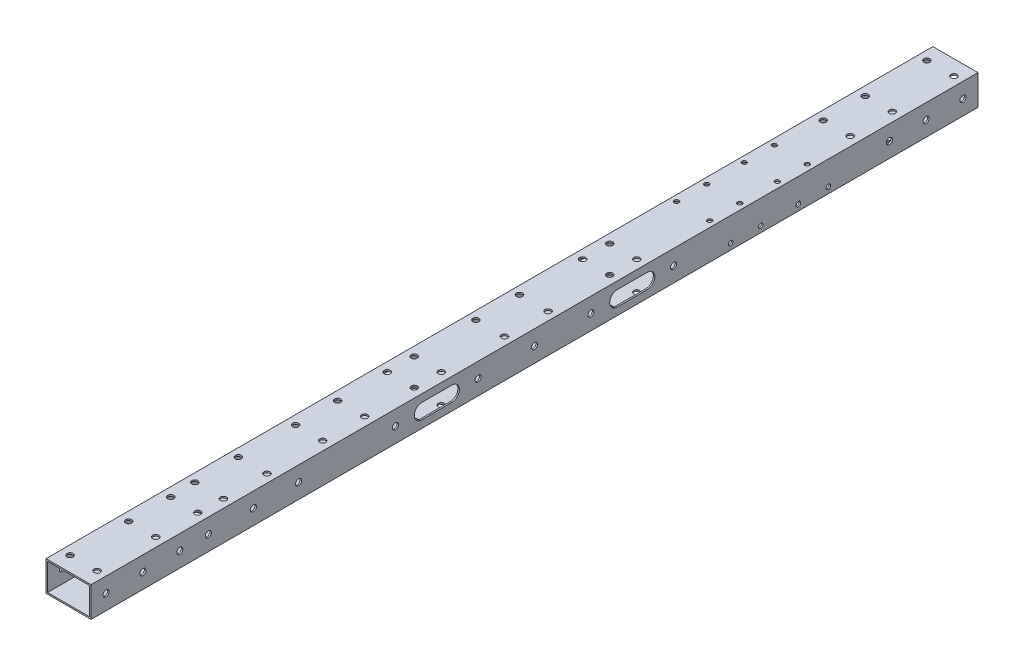
SolidWorks part; units mm, degrees
material "6063-T5"
ref_plane "前视基准面" through (0, 0, 0) normal (0, 0, 1) x (1, 0, 0)
ref_plane "上视基准面" through (0, 0, 0) normal (0, 1, 0) x (1, 0, 0)
ref_plane "右视基准面" through (0, 0, 0) normal (1, 0, 0) x (0, 0, -1)
sketch "草图1" plane through (0, 0, 0) normal (0, 0, 1) x (1, 0, 0)
  line L0 (-14, -9) -> (-14, 9)
  line L1 (-15, -10) -> (15, -10)
  line L2 (-15, -10) -> (-15, 10)
  line L3 (-15, 10) -> (15, 10)
  line L4 (15, -10) -> (15, 10)
  line L5 (0, 10) -> (0, -10) construction
  line L6 (-15, 0) -> (15, 0) construction
  line L7 (-14, 9) -> (14, 9)
  line L8 (14, -9) -> (14, 9)
  line L9 (-14, -9) -> (14, -9)
  point P0 (0, 0)
  dimension "D1" = 20
  dimension "D2" = 30
  dimension "D3" = 1
extrude "凸台-拉伸1" add sketch "草图1" along normal mid plane 590
sketch "草图2" [suppressed] plane through (15, 0, 0) normal (1, 0, 0) x (0, 0, -1)
  line L0 (-295, 10) -> (295, 10) construction
  line L1 (209, 10) -> (295, 10)
  line L2 (209, 10) -> (209, -10)
  line L3 (209, -10) -> (295, -10)
  line L4 (295, 10) -> (295, -10)
  dimension "D1" = 86
extrude "切除-拉伸1" [suppressed] cut sketch "草图2" against normal blind 60
sketch "草图4" [suppressed] plane through (0, 10, 0) normal (0, 1, 0) x (1, 0, 0)
  circle A0 centre (0, 0) radius 5
  dimension "D1" = 10
extrude "切除-拉伸3" [suppressed] cut sketch "草图4" against normal mid plane 64
sketch "草图5" plane through (0, 9, 0) normal (0, -1, 0) x (1, 0, 0)
  line L0 (-15, 295) -> (-15, -295) construction
  line L1 (-9.5, 14.5) -> (9.5, 14.5) construction
  line L2 (-9.5, 14.5) -> (-9.5, -14.5) construction
  line L3 (-9.5, -14.5) -> (9.5, -14.5) construction
  line L4 (9.5, 14.5) -> (9.5, -14.5) construction
  line L5 (-9.5, 14.5) -> (9.5, -14.5) construction
  line L6 (-9.5, -14.5) -> (9.5, 14.5) construction
  line L7 (-9.5, 201.5) -> (9.5, 201.5) construction
  line L8 (-9.5, 201.5) -> (-9.5, 172.5) construction
  line L13 (-9.5, 172.5) -> (9.5, 172.5) construction
  line L14 (9.5, 201.5) -> (9.5, 172.5) construction
  line L15 (-15, 295) -> (15, 295) construction
  line L16 (15, 295) -> (15, -295) construction
  line L17 (-9.5, -172.5) -> (9.5, -172.5) construction
  line L18 (-9.5, -172.5) -> (-9.5, -201.5) construction
  line L19 (-9.5, -201.5) -> (9.5, -201.5) construction
  line L20 (9.5, -172.5) -> (9.5, -201.5) construction
  line L21 (-15, -295) -> (15, -295) construction
  circle A4 centre (9.5, -201.5) radius 1.65 construction
  circle A5 centre (9.5, -172.5) radius 1.65 construction
  circle A6 centre (-9.5, -201.5) radius 1.65 construction
  circle A7 centre (-9.5, -172.5) radius 1.65 construction
  circle A8 centre (-9.5, -172.5) radius 2.025
  circle A9 centre (9.5, -172.5) radius 2.025
  circle A10 centre (-9.5, -201.5) radius 2.025
  circle A11 centre (9.5, -201.5) radius 2.025
  circle A20 centre (9.5, 172.5) radius 1.65 construction
  circle A21 centre (-9.5, 172.5) radius 1.65 construction
  circle A22 centre (9.5, 201.5) radius 1.65 construction
  circle A23 centre (-9.5, 201.5) radius 1.65 construction
  circle A24 centre (9.5, -14.5) radius 1.65 construction
  circle A25 centre (9.5, 14.5) radius 1.65 construction
  circle A26 centre (-9.5, -14.5) radius 1.65 construction
  circle A27 centre (-9.5, 14.5) radius 1.65 construction
  circle A28 centre (-9.5, -14.5) radius 2.025
  circle A29 centre (9.5, -14.5) radius 2.025
  circle A30 centre (-9.5, 14.5) radius 2.025
  circle A31 centre (9.5, 14.5) radius 2.025
  circle A32 centre (-9.5, 172.5) radius 2.025
  circle A33 centre (-9.5, 201.5) radius 2.025
  circle A34 centre (9.5, 201.5) radius 2.025
  circle A35 centre (9.5, 172.5) radius 2.025
  point P1 (0, 0)
  point P3 (-9.5, 187)
  dimension "D1" = 4.05
  dimension "D2" = 29
  dimension "D5" = 29
  dimension "D3" = 19
  dimension "D4" = 19
  dimension "D6" = 5.5
  dimension "D7" = 93.5
  dimension "D8" = 5.5
  dimension "D9" = 5.5
  dimension "D10" = 122.5
  dimension "D11" = 29
extrude "切除-拉伸4" cut sketch "草图5" against normal mid plane 10
sketch "草图7" plane through (0, -9, 0) normal (0, 1, 0) x (1, 0, 0)
  circle A0 centre (-9.5, 201.5) radius 3.8
  circle A1 centre (9.5, 201.5) radius 3.8
  circle A2 centre (-9.5, 172.5) radius 3.8
  circle A3 centre (9.5, 172.5) radius 3.8
  circle A4 centre (-9.5, 14.5) radius 3.8
  circle A5 centre (9.5, 14.5) radius 3.8
  circle A6 centre (-9.5, -14.5) radius 3.8
  circle A7 centre (9.5, -14.5) radius 3.8
  circle A8 centre (-9.5, -172.5) radius 3.8
  circle A9 centre (9.5, -172.5) radius 3.8
  circle A10 centre (-9.5, -201.5) radius 3.8
  circle A11 centre (9.5, -201.5) radius 3.8
  dimension "D1" = 7.6
extrude "切除-拉伸5" cut sketch "草图7" against normal mid plane 10
sketch "草图8" [suppressed] plane through (15, 0, 0) normal (1, 0, 0) x (0, 0, -1)
  circle A0 centre (-151, 0) radius 2.025 construction
  circle A1 centre (-185, 0) radius 2.025 construction
  circle A2 centre (-219, 0) radius 2.025 construction
  circle A3 centre (-151, 0) radius 2.025
  circle A4 centre (-185, 0) radius 2.025
  circle A5 centre (-219, 0) radius 2.025
  circle A6 centre (36, 0) radius 2.025 construction
  circle A7 centre (2, 0) radius 2.025 construction
  circle A8 centre (-32, 0) radius 2.025 construction
  circle A9 centre (36, 0) radius 2.025
  circle A10 centre (2, 0) radius 2.025
  circle A11 centre (-32, 0) radius 2.025
extrude "切除-拉伸6" [suppressed] cut sketch "草图8" against normal blind 74
sketch "草图9" [suppressed] plane through (-15, 0, 0) normal (-1, 0, 0) x (0, 0, 1)
  circle A0 centre (-155, 0) radius 2.025 construction
  circle A1 centre (-189, 5) radius 1.525 construction
  circle A2 centre (-203, 0) radius 2.025 construction
  circle A3 centre (-155, 0) radius 2.025
  circle A4 centre (-189, 5) radius 1.525
  circle A5 centre (-203, 0) radius 2.025
extrude "切除-拉伸7" [suppressed] cut sketch "草图9" against normal blind 114
sketch "草图10" [suppressed] plane through (0, -10, 0) normal (0, -1, 0) x (1, 0, 0)
  circle A0 centre (0, -75) radius 2.025 construction
  circle A1 centre (0, -109) radius 2.025 construction
  circle A2 centre (0, -143) radius 2.025 construction
  circle A3 centre (0, -75) radius 2.025
  circle A4 centre (0, -109) radius 2.025
  circle A5 centre (0, -143) radius 2.025
extrude "切除-拉伸8" [suppressed] cut sketch "草图10" against normal blind 70
sketch "草图11" plane through (15, 0, 0) normal (1, 0, 0) x (0, 0, -1)
  line L0 (-295, -10) -> (-295, 10) construction
  line L1 (-295, 10) -> (295, 10) construction
  circle A9 centre (-236, 0) radius 2.025 construction
  circle A10 centre (-260.5, 0) radius 2.025 construction
  circle A11 centre (-285, 0) radius 2.025 construction
  circle A12 centre (217, 0) radius 2.025
  circle A13 centre (187, 0) radius 2.025
  circle A14 centre (157, 0) radius 2.025
  circle A15 centre (30, 0) radius 2.025
  circle A16 centre (0, 0) radius 2.025
  circle A17 centre (-30, 0) radius 2.025
  circle A18 centre (-157, 0) radius 2.025
  circle A19 centre (-187, 0) radius 2.025
  circle A20 centre (-217, 0) radius 2.025
  circle A21 centre (-236, 0) radius 2.025
  circle A22 centre (-260.5, 0) radius 2.025
  circle A23 centre (-285, 0) radius 2.025
  dimension "D1" = 30
  dimension "D3" = 78
  dimension "D4" = 30
  dimension "D5" = 30
  dimension "D6" = 10
  dimension "D7" = 127
  dimension "D8" = 127
  dimension "D9" = 30
  dimension "D10" = 30
  dimension "D2" = 30
extrude "切除-拉伸9" cut sketch "草图11" against normal blind 113
sketch "草图12" [suppressed] plane through (0, 10, 0) normal (0, 1, 0) x (1, 0, 0)
  circle A0 centre (0, 36.5) radius 2.025 construction
  circle A1 centre (0, 18.5) radius 2.025 construction
  circle A2 centre (0, 36.5) radius 2.025
  circle A3 centre (0, 18.5) radius 2.025
extrude "切除-拉伸10" [suppressed] cut sketch "草图12" against normal blind 80
sketch "草图13" [suppressed] plane through (-15, 0, 0) normal (-1, 0, 0) x (0, 0, 1)
  circle A0 centre (28, 0) radius 2.025 construction
  circle A1 centre (3.5, 0) radius 2.025 construction
  circle A2 centre (28, 0) radius 2.025
  circle A3 centre (3.5, 0) radius 2.025
extrude "切除-拉伸11" [suppressed] cut sketch "草图13" against normal blind 80
sketch "草图14" [suppressed] plane through (0, -9, 0) normal (0, 1, 0) x (1, 0, 0)
  circle A0 centre (-7.5, 45.55) radius 1.5 construction
  circle A1 centre (-7.5, 35.55) radius 1.5 construction
  circle A2 centre (7.5, 45.55) radius 1.5 construction
  circle A3 centre (7.5, 35.55) radius 1.5 construction
  circle A4 centre (7.5, 90.55) radius 1.5 construction
  circle A5 centre (7.5, 80.55) radius 1.5 construction
  circle A6 centre (-7.5, 90.55) radius 1.5 construction
  circle A7 centre (-7.5, 80.55) radius 1.5 construction
  circle A8 centre (-7.5, 45.55) radius 1.5
  circle A9 centre (-7.5, 35.55) radius 1.5
  circle A10 centre (7.5, 45.55) radius 1.5
  circle A11 centre (7.5, 35.55) radius 1.5
  circle A12 centre (7.5, 90.55) radius 1.5
  circle A13 centre (7.5, 80.55) radius 1.5
  circle A14 centre (-7.5, 90.55) radius 1.5
  circle A15 centre (-7.5, 80.55) radius 1.5
extrude "切除-拉伸12" [suppressed] cut sketch "草图14" against normal blind 10
sketch "草图15" [suppressed] plane through (0, -10, 0) normal (0, -1, 0) x (1, 0, 0)
  circle A0 centre (9, 66) radius 2.025 construction
  circle A1 centre (-9, 66) radius 2.025 construction
  circle A2 centre (9, 94) radius 2.025 construction
  circle A3 centre (-9, 94) radius 2.025 construction
  circle A4 centre (9, 66) radius 2.025
  circle A5 centre (-9, 66) radius 2.025
  circle A6 centre (9, 94) radius 2.025
  circle A7 centre (-9, 94) radius 2.025
extrude "切除-拉伸13" [suppressed] cut sketch "草图15" against normal up to surface (20 mm away)
sketch "草图16" [suppressed] plane through (-15, 0, 0) normal (-1, 0, 0) x (0, 0, 1)
  line L0 (0, 0) -> (0, 10) construction
  line L1 (84.5, 10) -> (-84.5, 10) construction
  circle A0 centre (59.5, 0) radius 1.525 construction
  circle A1 centre (79.5, 0) radius 1.525 construction
  circle A2 centre (59.5, 0) radius 1.525
  circle A3 centre (79.5, 0) radius 1.525
  circle A4 centre (-79.5, 0) radius 1.525
  circle A5 centre (-59.5, 0) radius 1.525
sketch "草图17" [suppressed] plane through (15, 0, 0) normal (1, 0, 0) x (0, 0, -1)
  circle A0 centre (94, 0) radius 1.525 construction
  circle A1 centre (66, 0) radius 1.525 construction
  circle A2 centre (94, 0) radius 1.525
  circle A3 centre (66, 0) radius 1.525
extrude "切除-拉伸14" [suppressed] cut sketch "草图16" against normal up to surface (30 mm away)
extrude "切除-拉伸15" [suppressed] cut sketch "草图17" against normal up to surface (30 mm away)
sketch "草图18" plane through (0, -10, 0) normal (0, -1, 0) x (1, 0, 0)
  line L0 (-429.5, 50) -> (160.5, 50) construction
  line L1 (-429.5, 80) -> (160.5, 80) construction
  line L2 (-15, 50) -> (15, 50) construction
  line L3 (-15, 80) -> (15, 80) construction
  line L4 (15, 295) -> (15, -295) construction
  line L5 (-15, 295) -> (-15, -295) construction
  line L6 (-15, 80) -> (15, 50) construction
  line L8 (-9, 56) -> (9, 56) construction
  line L9 (-9, 56) -> (-9, 74) construction
  line L10 (-9, 74) -> (9, 74) construction
  line L11 (9, 56) -> (9, 74) construction
  line L12 (0, 74) -> (0, 56) construction
  line L13 (-9, 65) -> (9, 65) construction
  circle A0 centre (-9, 74) radius 2.025
  circle A1 centre (9, 74) radius 2.025
  circle A2 centre (-9, 56) radius 2.025
  circle A3 centre (9, 56) radius 2.025
  point P4 (0, 65)
  dimension "D3" = 4.05
  dimension "D1" = 6
  dimension "D2" = 6
extrude "切除-拉伸16" cut sketch "草图18" against normal blind 90
mirror "镜向1" about plane through (0, 0, 0) normal (0, 0, 1) of "切除-拉伸16"
sketch "草图19" [suppressed] plane through (0, 10, 0) normal (0, 1, 0) x (1, 0, 0)
  line L0 (-15, -275) -> (15, -275) construction
  line L1 (-15, -295) -> (-15, 209) construction
  line L2 (15, -295) -> (-15, -295) construction
  line L3 (15, -295) -> (15, 209) construction
  line L4 (-15, -275) -> (15, -295) construction
  line L6 (-10, -290) -> (10, -290) construction
  line L7 (-10, -290) -> (-10, -280) construction
  line L8 (-10, -280) -> (10, -280) construction
  line L9 (10, -290) -> (10, -280) construction
  line L10 (0, -280) -> (0, -290) construction
  line L11 (-10, -285) -> (10, -285) construction
  circle A0 centre (-10, -285) radius 2.025
  circle A1 centre (10, -285) radius 2.025
  point P6 (0, -285)
  dimension "D4" = 4.05
  dimension "D1" = 20
  dimension "D2" = 5
  dimension "D3" = 5
extrude "切除-拉伸17" [suppressed] cut sketch "草图19" against normal blind 10
sketch "草图20" [suppressed] plane through (0, 10, 0) normal (0, 1, 0) x (1, 0, 0)
  circle A0 centre (-10, -151) radius 2.025 construction
  circle A1 centre (10, -151) radius 2.025 construction
  circle A2 centre (-10, -151) radius 2.025
  circle A3 centre (10, -151) radius 2.025
extrude "切除-拉伸18" [suppressed] cut sketch "草图20" against normal blind 10
sketch "草图21" plane through (15, 0, 0) normal (1, 0, 0) x (0, 0, -1)
  line L0 (-40, 290) -> (-40, -10) construction
  line L1 (-90, 290) -> (-90, -10) construction
  line L2 (-40, 10) -> (-40, -10) construction
  line L3 (-90, 10) -> (-90, -10) construction
  line L4 (-295, 10) -> (295, 10) construction
  line L5 (-90, 10) -> (-40, -10) construction
  line L6 (-84, 0) -> (-46, 0) construction
  circle A0 centre (-46, 0) radius 2.025
  circle A1 centre (-84, 0) radius 2.025
  point P11 (-65, 0)
  dimension "D2" = 4.05
  dimension "D1" = 6
extrude "切除-拉伸19" cut sketch "草图21" against normal blind 126
sketch "草图22" plane through (0, 10, 0) normal (0, 1, 0) x (1, 0, 0)
  line L0 (15, -275) -> (-15, -275) construction
  line L1 (15, -295) -> (15, 295) construction
  line L2 (-15, -295) -> (-15, 295) construction
  line L3 (15, -295) -> (-15, -295) construction
  line L4 (-15, -275) -> (15, -295) construction
  line L5 (-9, -285) -> (9, -285) construction
  line L6 (0, 0) -> (95.2431, 0) construction
  line L7 (-9, 285) -> (9, 285) construction
  line L8 (-15, 275) -> (15, 295) construction
  line L9 (15, 275) -> (-15, 275) construction
  circle A0 centre (9, -285) radius 2.025 construction
  circle A1 centre (-9, -285) radius 2.025 construction
  circle A2 centre (-9, 285) radius 2.025
  circle A3 centre (9, 285) radius 2.025
  point P13 (0, -285)
  point P25 (0, 285)
  dimension "D3" = 4.05
  dimension "D1" = 20
  dimension "D2" = 6
extrude "切除-拉伸20" cut sketch "草图22" against normal blind 10
sketch "草图23" [suppressed] plane through (-15, 0, 0) normal (-1, 0, 0) x (0, 0, 1)
  circle A0 centre (44, 0) radius 2.025 construction
  circle A1 centre (82, 0) radius 2.025 construction
  circle A2 centre (44, 0) radius 2.025
  circle A3 centre (82, 0) radius 2.025
extrude "切除-拉伸21" [suppressed] cut sketch "草图23" against normal blind 70
sketch "草图24" [suppressed] plane through (-15, 0, 0) normal (-1, 0, 0) x (0, 0, 1)
  circle A0 centre (44, 0) radius 4
  circle A1 centre (82, 0) radius 4
  dimension "D1" = 8
extrude "切除-拉伸22" [suppressed] cut sketch "草图24" against normal blind 10
sketch "草图25" [suppressed] plane through (0, -10, 0) normal (0, -1, 0) x (1, 0, 0)
  line L0 (-15, 46.025) -> (-15, 41.975) construction
  line L1 (-15, 84.025) -> (-15, 79.975) construction
  line L2 (-15, 46.025) -> (-15, 41.975) construction
  line L3 (-15, 84.025) -> (-15, 79.975) construction
  line L4 (-15, 82) -> (15, 82) construction
  line L5 (15, 295) -> (15, -209) construction
  line L6 (-15, 44) -> (15, 82) construction
  line L7 (0, 45.5) -> (0, 80.5) construction
  line L8 (-7, 45.5) -> (-7, 80.5)
  line L9 (7, 45.5) -> (7, 80.5)
  arc A0 (-7, 45.5) -> (7, 45.5) centre (0, 45.5) ccw
  arc A1 (7, 80.5) -> (-7, 80.5) centre (0, 80.5) ccw
  point P11 (0, 63)
  dimension "D1" = 7
  dimension "D2" = 35
extrude "切除-拉伸23" [suppressed] cut sketch "草图25" against normal blind 10 from surface
sketch "草图26" plane through (0, -10, 0) normal (0, -1, 0) x (1, 0, 0)
  line L0 (-11, 144) -> (-11, 124) construction
  line L1 (-15, 295) -> (-15, -295) construction
  line L2 (0, 0) -> (0, 192.5481) construction
  line L3 (11, 144) -> (11, 124) construction
  circle A0 centre (-11, 124) radius 1.525
  circle A1 centre (-11, 144) radius 1.525
  circle A2 centre (-9, 74) radius 2.025 construction
  circle A3 centre (11, 144) radius 1.525
  circle A4 centre (11, 124) radius 1.525
  dimension "D3" = 3.05
  dimension "D4" = 50
  dimension "D1" = 20
  dimension "D2" = 4
extrude "切除-拉伸24" cut sketch "草图26" against normal blind 10
sketch "草图27" plane through (-15, 0, 0) normal (-1, 0, 0) x (0, 0, 1)
  circle A0 centre (114, -6) radius 1.25 construction
  circle A1 centre (134, -6) radius 1.25 construction
  circle A2 centre (114, -6) radius 1.25 construction
  circle A3 centre (134, -6) radius 1.25 construction
  circle A4 centre (134, -6) radius 1.525
  circle A5 centre (114, -6) radius 1.525
  dimension "D1" = 3.05
extrude "切除-拉伸25" cut sketch "草图27" against normal blind 100
sketch "草图28" plane through (15, 0, 0) normal (1, 0, 0) x (0, 0, -1)
  line L0 (-53.975, 10) -> (-58.025, 10) construction
  line L1 (-71.975, 10) -> (-76.025, 10) construction
  line L2 (-53.975, 10) -> (-58.025, 10) construction
  line L3 (-71.975, 10) -> (-76.025, 10) construction
  line L4 (-74, 10) -> (-74, -10) construction
  line L5 (-295, -10) -> (295, -10) construction
  line L6 (-56, 10) -> (-56, -10) construction
  line L7 (-74, 0) -> (-56, 0) construction
  line L8 (-71, 0) -> (-59, 0) construction
  line L9 (-71, 5) -> (-59, 5)
  line L10 (-71, -5) -> (-59, -5)
  arc A0 (-71, 5) -> (-71, -5) centre (-71, 0) ccw
  arc A1 (-59, -5) -> (-59, 5) centre (-59, 0) ccw
  point P14 (-65, 0)
  dimension "D1" = 5
  dimension "D2" = 12
extrude "切除-拉伸26" cut sketch "草图28" against normal blind 100
mirror "镜向2" about plane through (0, 0, 0) normal (0, 0, 1) of "切除-拉伸26"
sketch "草图29" [suppressed] plane through (0, 10, 0) normal (0, 1, 0) x (1, 0, 0)
  circle A0 centre (-5.25, 9.0933) radius 1.7 construction
  circle A1 centre (5.25, 9.0933) radius 1.7 construction
  circle A2 centre (5.25, -9.0933) radius 1.7 construction
  circle A3 centre (-5.25, -9.0933) radius 1.7 construction
  circle A4 centre (-5.25, 9.0933) radius 1.7 construction
  circle A5 centre (5.25, 9.0933) radius 1.7 construction
  circle A6 centre (5.25, -9.0933) radius 1.7 construction
  circle A7 centre (-5.25, -9.0933) radius 1.7 construction
  circle A8 centre (5.25, 9.0933) radius 1.525
  circle A9 centre (-5.25, 9.0933) radius 1.525
  circle A10 centre (-5.25, -9.0933) radius 1.525
  circle A11 centre (5.25, -9.0933) radius 1.525
  dimension "D1" = 3.05
extrude "切除-拉伸27" [suppressed] cut sketch "草图29" against normal blind 60
sketch "草图30" [suppressed] plane through (15, 0, 0) normal (1, 0, 0) x (0, 0, -1)
  line L0 (10.6183, 10) -> (7.5683, 10) construction
  line L1 (-7.5683, 10) -> (-10.6183, 10) construction
  line L2 (10.6183, 10) -> (7.5683, 10) construction
  line L3 (-7.5683, 10) -> (-10.6183, 10) construction
  line L4 (-9.0933, 10) -> (-9.0933, -10) construction
  line L5 (-84.5, -10) -> (84.5, -10) construction
  line L6 (9.0933, 10) -> (9.0933, -10) construction
  line L7 (-6.5, 0) -> (6.5, 0) construction
  line L8 (-6.5, 5) -> (6.5, 5)
  line L9 (-6.5, -5) -> (6.5, -5)
  arc A0 (-6.5, 5) -> (-6.5, -5) centre (-6.5, 0) ccw
  arc A1 (6.5, -5) -> (6.5, 5) centre (6.5, 0) ccw
  point P12 (0, 0)
  dimension "D1" = 5
  dimension "D2" = 13
extrude "切除-拉伸28" [suppressed] cut sketch "草图30" against normal blind 60
sketch "草图31" plane through (0, 10, 0) normal (0, 1, 0) x (1, 0, 0)
  circle A4 centre (0, 72) radius 2.025 construction
  circle A5 centre (0, 132) radius 2.025 construction
  circle A6 centre (0, 72) radius 2.025
  circle A7 centre (0, 132) radius 2.025
extrude "切除-拉伸29" cut sketch "草图31" against normal blind 50
sketch "草图32" plane through (-15, 0, 0) normal (-1, 0, 0) x (0, 0, 1)
  circle A0 centre (46, 0) radius 3.75
  circle A1 centre (84, 0) radius 3.75
  dimension "D1" = 7.5
extrude "切除-拉伸30" cut sketch "草图32" against normal blind 10
sketch "草图33" [suppressed] plane through (0, 10, 0) normal (0, 1, 0) x (1, 0, 0)
  line L0 (0, -171) -> (0, -201) construction
  line L1 (6, -171) -> (6, -201)
  line L2 (-6, -171) -> (-6, -201)
  arc A0 (6, -171) -> (-6, -171) centre (0, -171) ccw
  arc A1 (-6, -201) -> (6, -201) centre (0, -201) ccw
  circle A2 centre (10, -151) radius 2.025 construction
  point P3 (0, -186)
  dimension "D2" = 6
  dimension "D1" = 20
  dimension "D3" = 30
extrude "切除-拉伸31" [suppressed] cut sketch "草图33" against normal up to surface (20 mm away)
sketch "草图34" [suppressed] plane through (0, 10, 0) normal (0, 1, 0) x (1, 0, 0)
  line L0 (15, -0.025) -> (15, 4.025) construction
  line L1 (15, -0.025) -> (15, 4.025) construction
  line L2 (15, 2) -> (-15, 2) construction
  line L3 (-15, -295) -> (-15, 209) construction
  line L4 (0, 2) -> (0, 17) construction
  circle A0 centre (0, 17) radius 1.525
  circle A1 centre (0, -13) radius 1.525
  dimension "D2" = 3.05
  dimension "D1" = 15
extrude "切除-拉伸32" [suppressed] cut sketch "草图34" against normal blind 50
sketch "草图36" plane through (0, 10, 0) normal (0, 1, 0) x (1, 0, 0)
  line L0 (15, -295) -> (15, 295) construction
  line L1 (-9, 244) -> (9, 244) construction
  line L2 (-9, 244) -> (-9, 216) construction
  line L3 (-9, 216) -> (9, 216) construction
  line L4 (9, 244) -> (9, 216) construction
  line L5 (-15, -295) -> (-15, 295) construction
  line L6 (15, 295) -> (-15, 295) construction
  circle A4 centre (-9, 244) radius 2.025
  circle A5 centre (-9, 216) radius 2.025
  circle A6 centre (9, 216) radius 2.025
  circle A7 centre (9, 244) radius 2.025
  dimension "D5" = 4.05
  dimension "D1" = 6
  dimension "D2" = 6
  dimension "D3" = 28
  dimension "D4" = 79
extrude "切除-拉伸33" cut sketch "草图36" against normal blind 37
sketch "草图37" plane through (0, -10, 0) normal (0, -1, 0) x (1, 0, 0)
  circle A0 centre (-9, -216) radius 3.8
  circle A1 centre (9, -216) radius 3.8
  circle A2 centre (-9, -244) radius 3.8
  circle A3 centre (9, -244) radius 3.8
  circle A4 centre (-9.5, -201.5) radius 3.8 construction
extrude "切除-拉伸34" cut sketch "草图37" against normal blind 10
mirror "镜向3" about plane through (0, 0, 0) normal (0, 0, 1) of "切除-拉伸34", "切除-拉伸33"
sketch "草图38" plane through (15, 0, 0) normal (1, 0, 0) x (0, 0, -1)
  circle A0 centre (-84, 0) radius 2.5
  circle A1 centre (-46, 0) radius 2.5
  dimension "D1" = 5
extrude "凸台-拉伸2" add sketch "草图38" against normal up to surface (1 mm away) up to face at (14, 0, 65)
sketch "草图39" plane through (-15, 0, 0) normal (-1, 0, 0) x (0, 0, 1)
  circle A0 centre (84, 0) radius 6
  circle A1 centre (46, 0) radius 6
  dimension "D1" = 12
extrude "凸台-拉伸3" add sketch "草图39" against normal up to surface (1 mm away) up to face at (-14, 0, 42.25)
sketch "草图40" plane through (0, 10, 0) normal (0, 1, 0) x (1, 0, 0)
  circle A0 centre (0, 72) radius 2.025
extrude "凸台-拉伸4" add sketch "草图40" against normal up to surface (1 mm away) up to face at (9, 9, 241.975)
sketch "草图41" plane through (0, -10, 0) normal (0, -1, 0) x (1, 0, 0)
  circle A0 centre (0, -72) radius 2.025
extrude "凸台-拉伸5" add sketch "草图41" against normal up to surface (1 mm away) up to face at (9, -9, 219.8)
sketch "草图42" plane through (-15, 0, 0) normal (-1, 0, 0) x (0, 0, 1)
  line L0 (-75, 0) -> (-55, 0) construction
  line L1 (-75, 5) -> (-55, 5)
  line L2 (-75, -5) -> (-55, -5)
  line L3 (-59, 5) -> (-71, 5) construction
  line L4 (0, 0) -> (0, 10) construction
  line L5 (295, 10) -> (-295, 10) construction
  line L6 (75, 0) -> (55, 0) construction
  line L7 (75, 5) -> (55, 5)
  line L8 (75, -5) -> (55, -5)
  arc A0 (-75, 5) -> (-75, -5) centre (-75, 0) ccw
  arc A1 (-55, -5) -> (-55, 5) centre (-55, 0) ccw
  arc A2 (75, 5) -> (75, -5) centre (75, 0) cw
  arc A3 (55, -5) -> (55, 5) centre (55, 0) cw
  point P2 (-65, 0)
  point P10 (-65, 5)
  point P13 (65, 0)
  dimension "D1" = 5
  dimension "D2" = 20
extrude "切除-拉伸36" cut sketch "草图42" against normal up to surface (30 mm away) up to face at (15, 0, 0)
sketch "草图43" plane through (-15, 0, 0) normal (-1, 0, 0) x (0, 0, 1)
  circle A0 centre (-30, 0) radius 2.5
  circle A1 centre (0, 0) radius 2.5
  circle A2 centre (30, 0) radius 2.5
  dimension "D1" = 5
extrude "凸台-拉伸6" add sketch "草图43" against normal up to surface (1 mm away) up to face at (-14, 0, -65)
sketch "草图44" plane through (15, 0, 0) normal (1, 0, 0) x (0, 0, -1)
  circle A0 centre (-30, 0) radius 2.5
  circle A1 centre (0, 0) radius 2.5
  circle A2 centre (30, 0) radius 2.5
  dimension "D1" = 5
extrude "凸台-拉伸7" add sketch "草图44" against normal up to surface (1 mm away) up to face at (14, 0, -65)
sketch "草图45" plane through (-15, 0, 0) normal (-1, 0, 0) x (0, 0, 1)
  line L0 (-65, 5) -> (-65, 10) construction
  line L1 (-55, 5) -> (-75, 5) construction
  line L2 (295, 10) -> (-295, 10) construction
  line L3 (0, 0) -> (0, 10) construction
  circle A0 centre (-92.5, 0) radius 2.025
  circle A1 centre (-37.5, 0) radius 2.025
  circle A2 centre (37.5, 0) radius 2.025
  circle A3 centre (92.5, 0) radius 2.025
  dimension "D1" = 4.05
  dimension "D2" = 55
extrude "切除-拉伸37" cut sketch "草图45" against normal up to surface (30 mm away) up to face at (15, 0, 0)
sketch "草图47" plane through (0, 10, 0) normal (0, 1, 0) x (1, 0, 0)
  line L1 (-12.8725, -260.1822) -> (12.8725, -260.1822)
  line L2 (-12.8725, -260.1822) -> (-12.8725, -210.1822)
  line L3 (-12.8725, -210.1822) -> (12.8725, -210.1822)
  line L4 (12.8725, -260.1822) -> (12.8725, -210.1822)
  line L5 (-12.8725, -260.1822) -> (12.8725, -210.1822) construction
  line L6 (-12.8725, -210.1822) -> (12.8725, -260.1822) construction
  point P0 (0, -235.1822)
  dimension "D1" = 50
extrude "凸台-拉伸8" add sketch "草图47" against normal up to surface (1 mm away) up to face at (9, 9, 241.975)
sketch "草图46" plane through (0, 10, 0) normal (0, 1, 0) x (1, 0, 0)
  line L0 (15, -295) -> (-15, -295) construction
  line L1 (-9, -246) -> (9, -246) construction
  line L2 (-9, -246) -> (-9, -218) construction
  line L3 (-9, -218) -> (9, -218) construction
  line L4 (9, -246) -> (9, -218) construction
  line L5 (-9, -246) -> (9, -218) construction
  line L6 (-9, -218) -> (9, -246) construction
  circle A1 centre (9, -218) radius 2.025
  circle A2 centre (9, -246) radius 2.025
  circle A3 centre (-9, -246) radius 2.025
  circle A4 centre (-9, -218) radius 2.025
  point P0 (0, -232)
  dimension "D1" = 4.05
  dimension "D2" = 49
  dimension "D3" = 28
  dimension "D4" = 18
extrude "切除-拉伸38" cut sketch "草图46" against normal up to surface (1 mm away) up to face at (9, 9, -246.025)
sketch "草图48" plane through (0, -10, 0) normal (0, -1, 0) x (1, 0, 0)
  line L0 (15, 295) -> (15, -295) construction
  line L1 (-15, 208.46) -> (15, 208.46)
  line L2 (-15, 208.46) -> (-15, 248.9585)
  line L3 (-15, 248.9585) -> (15, 248.9585)
  line L4 (15, 208.46) -> (15, 248.9585)
  line L5 (-15, 208.46) -> (15, 248.9585) construction
  line L6 (-15, 248.9585) -> (15, 208.46) construction
  point P0 (0, 228.7092)
extrude "凸台-拉伸9" add sketch "草图48" against normal up to surface (1 mm away) up to face at (9, -9, 219.8)
sketch "草图50" plane through (0, -9, 0) normal (0, 1, 0) x (1, 0, 0)
  line L1 (-9, -246) -> (9, -246) construction
  line L2 (-9, -246) -> (-9, -218) construction
  line L3 (-9, -218) -> (9, -218) construction
  line L4 (9, -246) -> (9, -218) construction
  circle A0 centre (-9, -246) radius 3.8
  circle A1 centre (-9, -218) radius 3.8
  circle A2 centre (9, -218) radius 3.8
  circle A3 centre (9, -246) radius 3.8
  dimension "D1" = 7.6
extrude "切除-拉伸40" cut sketch "草图50" against normal up to surface (1 mm away) up to face at (9, -10, -219.8)
sketch "草图51" plane through (0, -10, 0) normal (0, -1, 0) x (1, 0, 0)
  circle A0 centre (9.5, -201.5) radius 4.5
  circle A1 centre (-9.5, -201.5) radius 4.5
  circle A2 centre (-9.5, -172.5) radius 4.5
  circle A3 centre (9.5, -172.5) radius 4.5
  dimension "D1" = 9
extrude "凸台-拉伸10" add sketch "草图51" against normal up to surface (1 mm away) up to face at (9, -9, 249.8)
sketch "草图52" plane through (0, 10, 0) normal (0, 1, 0) x (1, 0, 0)
  circle A0 centre (-9.5, 172.5) radius 2.5
  circle A1 centre (-9.5, 201.5) radius 2.5
  circle A2 centre (9.5, 201.5) radius 2.5
  circle A3 centre (9.5, 172.5) radius 2.5
  dimension "D1" = 5
extrude "凸台-拉伸11" add sketch "草图52" against normal up to surface (1 mm away) up to face at (-9, 9, 215.975)
sketch "草图53" plane through (0, -10, 0) normal (0, -1, 0) x (1, 0, 0)
  circle A0 centre (0, -132) radius 2.5
  dimension "D1" = 5
extrude "凸台-拉伸12" add sketch "草图53" against normal up to surface (1 mm away) up to face at (9, -9, 249.8)
sketch "草图54" plane through (0, 10, 0) normal (0, 1, 0) x (1, 0, 0)
  circle A0 centre (0, 132) radius 2.5
  dimension "D1" = 5
extrude "凸台-拉伸13" add sketch "草图54" against normal up to surface (1 mm away) up to face at (-9, 9, 215.975)
sketch "草图55" plane through (0, -10, 0) normal (0, -1, 0) x (1, 0, 0)
  circle A0 centre (11, 124) radius 2
  circle A1 centre (11, 144) radius 2
  circle A2 centre (-11, 144) radius 2
  circle A3 centre (-11, 124) radius 2
  dimension "D1" = 4
extrude "凸台-拉伸14" add sketch "草图55" against normal up to surface (1 mm away) up to face at (9, -9, 249.8)
sketch "草图56" plane through (15, 0, 0) normal (1, 0, 0) x (0, 0, -1)
  circle A0 centre (-134, -6) radius 2
  circle A1 centre (-114, -6) radius 2
  dimension "D1" = 4
extrude "凸台-拉伸15" add sketch "草图56" against normal up to surface (1 mm away) up to face at (14, 0, -90.475)
sketch "草图57" plane through (-15, 0, 0) normal (-1, 0, 0) x (0, 0, 1)
  circle A0 centre (114, -6) radius 2
  circle A1 centre (134, -6) radius 2
  dimension "D1" = 4
extrude "凸台-拉伸16" add sketch "草图57" against normal up to surface (1 mm away) up to face at (-14, 0, -94.525)
sketch "草图58" plane through (0, -10, 0) normal (0, -1, 0) x (1, 0, 0)
  line L0 (-284, 141) -> (15, 141) construction
  line L1 (-9, 107) -> (9, 107) construction
  line L2 (-9, 107) -> (-9, 135) construction
  line L3 (-9, 135) -> (9, 135) construction
  line L4 (9, 107) -> (9, 135) construction
  line L5 (-9, 107) -> (9, 135) construction
  line L6 (-9, 135) -> (9, 107) construction
  circle A0 centre (-9, 135) radius 2.025
  circle A1 centre (-9, 107) radius 2.025
  circle A2 centre (9, 107) radius 2.025
  circle A3 centre (9, 135) radius 2.025
  point P0 (0, 121)
  dimension "D4" = 4.05
  dimension "D1" = 18
  dimension "D2" = 28
  dimension "D3" = 20
extrude "切除-拉伸41" cut sketch "草图58" against normal through all both and the other way through all
sketch "草图59" plane through (0, -10, 0) normal (0, -1, 0) x (1, 0, 0)
  circle A0 centre (-9, 135) radius 3.8
  circle A1 centre (-9, 107) radius 3.8
  circle A2 centre (9, 107) radius 3.8
  circle A3 centre (9, 135) radius 3.8
  dimension "D1" = 7.6
extrude "切除-拉伸42" cut sketch "草图59" against normal blind 3
sketch "草图61" plane through (0, -10, 0) normal (0, -1, 0) x (1, 0, 0)
  line L0 (15, 295) -> (15, -295) construction
  line L1 (-15, -295) -> (15, -295) construction
  line L2 (0, 0) -> (0, -2) construction
  circle A0 centre (11, -185.5) radius 1.525
  circle A1 centre (11, -165.5) radius 1.525
  circle A2 centre (11, -120.5) radius 1.525
  circle A3 centre (11, -140.5) radius 1.525
  circle A4 centre (-11, -140.5) radius 1.525
  circle A5 centre (-11, -120.5) radius 1.525
  circle A6 centre (-11, -165.5) radius 1.525
  circle A7 centre (-11, -185.5) radius 1.525
  dimension "D1" = 3.05
  dimension "D2" = 20
  dimension "D3" = 20
  dimension "D4" = 25
  dimension "D5" = 4
  dimension "D6" = 109.5
  dimension "D7" = 2
extrude "切除-拉伸43" cut sketch "草图61" against normal through all both and the other way through all
sketch "草图62" plane through (-15, 0, 0) normal (-1, 0, 0) x (0, 0, 1)
  circle A0 centre (-217, 0) radius 2.5
  circle A1 centre (-187, 0) radius 2.5
  circle A2 centre (-157, 0) radius 2.5
  dimension "D1" = 5
extrude "凸台-拉伸17" add sketch "草图62" against normal up to surface (1 mm away) up to face at (-14, 0, -94.525)
sketch "草图63" plane through (15, 0, 0) normal (1, 0, 0) x (0, 0, -1)
  circle A0 centre (157, 0) radius 2.5
  circle A1 centre (187, 0) radius 2.5
  circle A2 centre (217, 0) radius 2.5
  dimension "D1" = 5
extrude "凸台-拉伸18" add sketch "草图63" against normal up to surface (1 mm away) up to face at (14, 0, -90.475)
sketch "草图64" plane through (15, 0, 0) normal (1, 0, 0) x (0, 0, -1)
  line L0 (-295, -10) -> (295, -10) construction
  line L1 (295, -10) -> (295, 10) construction
  circle A0 centre (130.5, -6) radius 1.525
  circle A1 centre (150.5, -6) radius 1.525
  circle A2 centre (175.5, -6) radius 1.525
  circle A3 centre (195.5, -6) radius 1.525
  dimension "D1" = 3.05
  dimension "D3" = 99.5
  dimension "D4" = 20
  dimension "D5" = 20
  dimension "D6" = 25
  dimension "D2" = 4
extrude "切除-拉伸44" cut sketch "草图64" against normal through all both and the other way through all
mirror "镜向4" about plane through (0, 0, 0) normal (0, 0, 1) of "切除-拉伸9"
sketch "草图65" plane through (-15, 0, 0) normal (-1, 0, 0) x (0, 0, 1)
  circle A0 centre (-217, 0) radius 4
  circle A1 centre (-187, 0) radius 4
  circle A2 centre (-157, 0) radius 4
  dimension "D1" = 8
extrude "凸台-拉伸19" add sketch "草图65" against normal up to surface (1 mm away) up to face at (-14, 0, 27.975)
sketch "草图66" plane through (15, 0, 0) normal (1, 0, 0) x (0, 0, -1)
  circle A0 centre (157, 0) radius 4
  circle A1 centre (187, 0) radius 4
  circle A2 centre (217, 0) radius 4
  dimension "D1" = 8
extrude "凸台-拉伸20" add sketch "草图66" against normal up to surface (1 mm away) up to face at (14, 0, 32.025)
mirror "镜向5" about plane through (0, 0, 0) normal (0, 0, 1) of "切除-拉伸20"
sketch "草图67" plane through (-15, 0, 0) normal (-1, 0, 0) x (0, 0, 1)
  circle A0 centre (-30, 0) radius 2.5
  circle A1 centre (30, 0) radius 2.5
  dimension "D1" = 5
extrude "凸台-拉伸21" add sketch "草图67" against normal up to surface (1 mm away) up to face at (-14, 0, 27.975)
sketch "草图68" plane through (15, 0, 0) normal (1, 0, 0) x (0, 0, -1)
  circle A0 centre (-30, 0) radius 2.5
  circle A1 centre (30, 0) radius 2.5
  dimension "D1" = 5
extrude "凸台-拉伸22" add sketch "草图68" against normal up to surface (1 mm away) up to face at (14, 0, 32.025)
